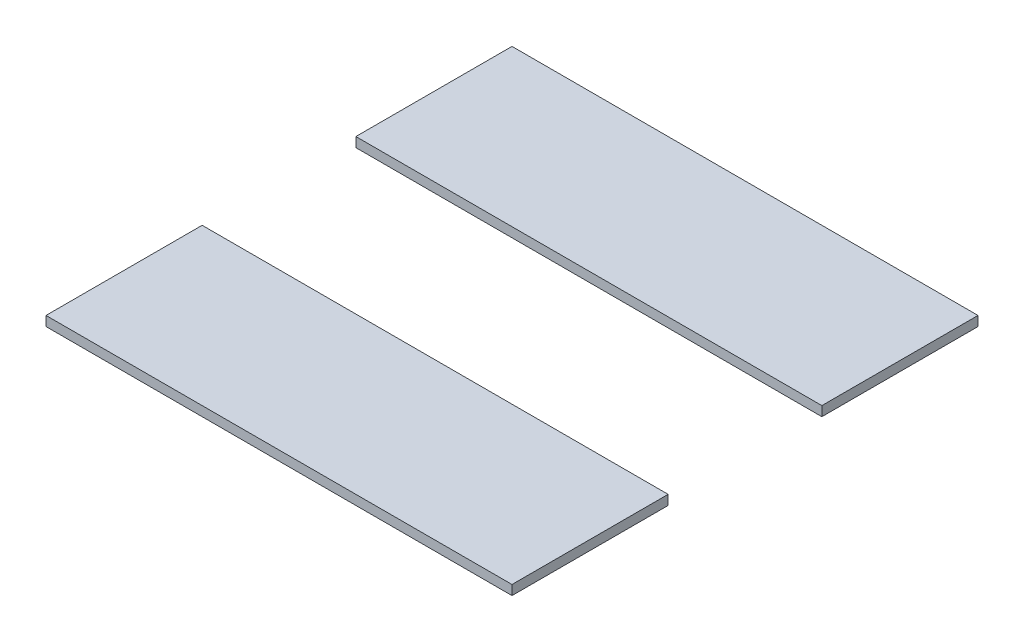
SolidWorks part; units mm, degrees
ref_plane "Front" through (0, 0, 0) normal (0, 0, 1) x (1, 0, 0)
ref_plane "Top" through (0, 0, 0) normal (0, 1, 0) x (1, 0, 0)
ref_plane "Right" through (0, 0, 0) normal (1, 0, 0) x (0, 0, -1)
sketch "Sketch1" plane through (0, 0, 0) normal (0, 1, 0) x (1, 0, 0)
  line L1 (-2454.275, 2454.275) -> (2454.275, 2454.275)
  line L2 (-2454.275, 2454.275) -> (-2454.275, -2454.275)
  line L3 (-2454.275, -2454.275) -> (2454.275, -2454.275)
  line L4 (2454.275, 2454.275) -> (2454.275, -2454.275)
  line L5 (-2454.275, 2454.275) -> (2454.275, -2454.275) construction
  line L6 (-2454.275, -2454.275) -> (2454.275, 2454.275) construction
  point P0 (0, 0)
  dimension "D1" = 4908.55
  dimension "D2" = 4908.55
extrude "Boss-Extrude1" add sketch "Sketch1" along normal blind 101.6
sketch "Sketch2" plane through (0, 101.6, 0) normal (0, 1, 0) x (1, 0, 0)
  line L0 (-2454.275, 2454.275) -> (-2454.275, -2454.275) construction
  line L1 (2454.275, -809.625) -> (-2454.275, -809.625)
  line L2 (2454.275, -809.625) -> (2454.275, 809.625)
  line L3 (2454.275, 809.625) -> (-2454.275, 809.625)
  line L4 (-2454.275, -809.625) -> (-2454.275, 809.625)
  line L5 (2454.275, -809.625) -> (-2454.275, 809.625) construction
  line L6 (2454.275, 809.625) -> (-2454.275, -809.625) construction
  point P0 (0, 0)
  dimension "D1" = 1619.25
extrude "Cut-Extrude1" cut sketch "Sketch2" against normal through all
